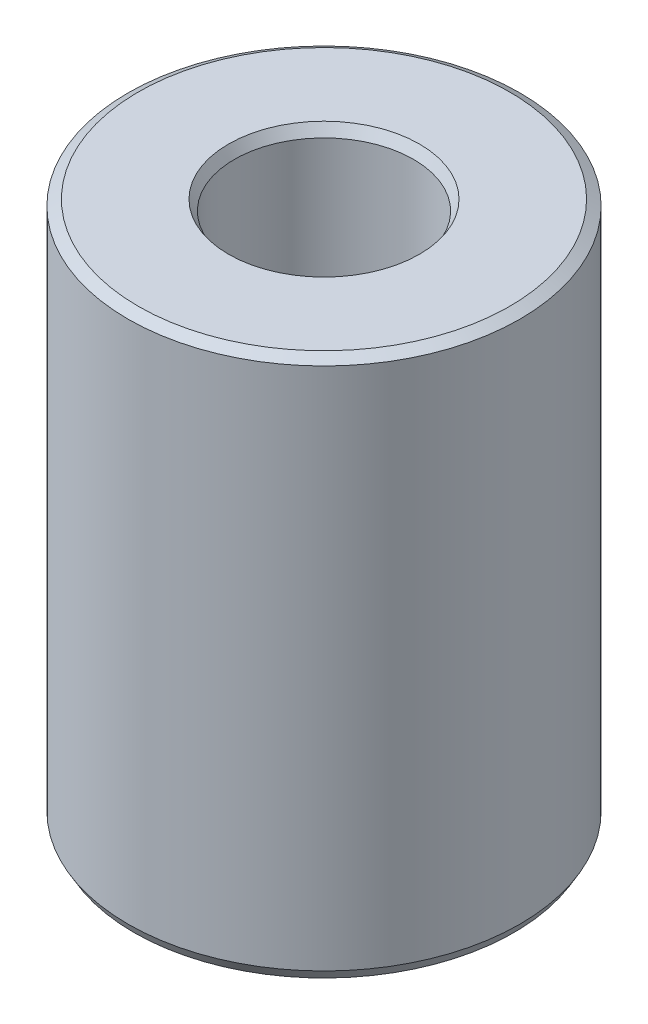
SolidWorks part; units mm, degrees
ref_plane "Front Plane" through (0, 0, 0) normal (0, 0, 1) x (1, 0, 0)
ref_plane "Top Plane" through (0, 0, 0) normal (0, 1, 0) x (1, 0, 0)
ref_plane "Right Plane" through (0, 0, 0) normal (1, 0, 0) x (0, 0, -1)
sketch "Sketch1" plane through (0, 0, 0) normal (0, 1, 0) x (1, 0, 0)
  circle A0 centre (0, 0) radius 30
  dimension "SLEEVE_OD" = 60
extrude "Boss-Extrude1" add sketch "Sketch1" along normal blind 82.6932
sketch "Sketch2" plane through (0, 0, 0) normal (0, 1, 0) x (1, 0, 0)
  circle A0 centre (0, 0) radius 13.7103
  dimension "BORE_D" = 27.4207
extrude "Cut-Extrude1" cut sketch "Sketch2" along normal through all
chamfer "Chamfer1" distance 0.9086 angle 60 4 edges at (0, 82.6932, 13.7103) (0, 0, 13.7103) (0, 0, 30) (0, 82.6932, 30) first distance on face at (0, 82.6932, 13.7103) first distance on face at (0, 0, 13.7103) first distance on face at (0, 82.6932, 30)
